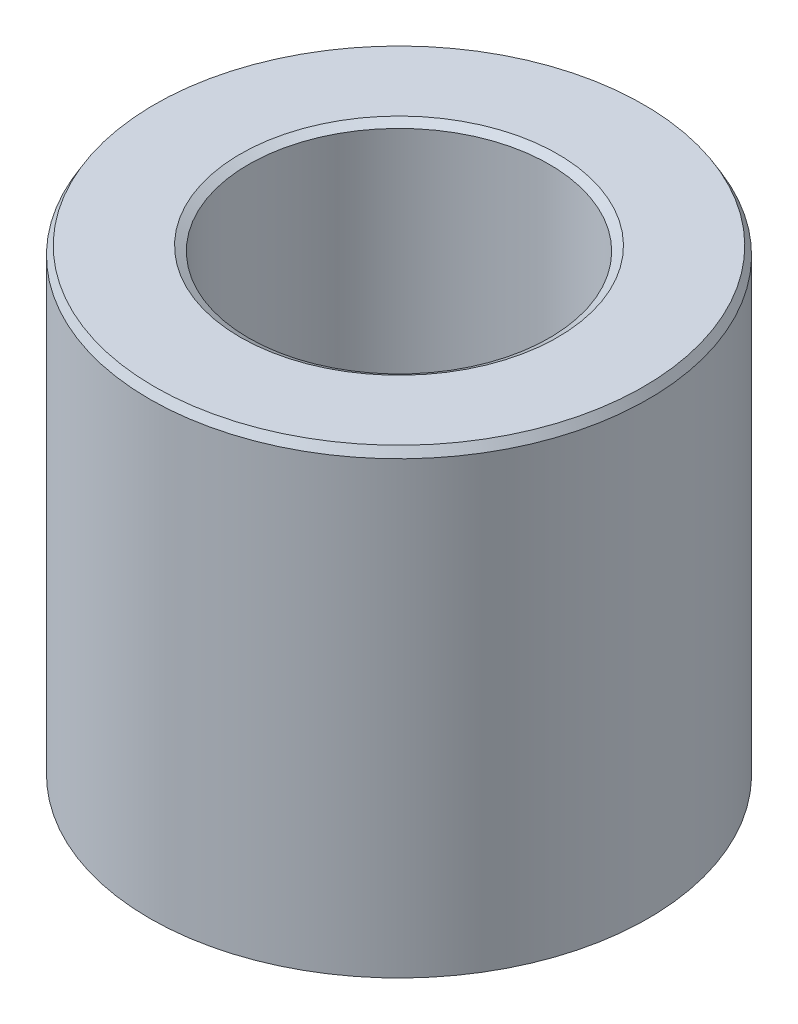
SolidWorks part; units mm, degrees
ref_plane "Front Plane" through (0, 0, 0) normal (0, 0, 1) x (1, 0, 0)
ref_plane "Top Plane" through (0, 0, 0) normal (0, 1, 0) x (1, 0, 0)
ref_plane "Right Plane" through (0, 0, 0) normal (1, 0, 0) x (0, 0, -1)
sketch "Sketch1" plane through (0, 0, 0) normal (0, 1, 0) x (1, 0, 0)
  circle A0 centre (0, 0) radius 60
  dimension "SLEEVE_OD" = 120
extrude "Boss-Extrude1" add sketch "Sketch1" along normal blind 111.3782
sketch "Sketch2" plane through (0, 0, 0) normal (0, 1, 0) x (1, 0, 0)
  circle A0 centre (0, 0) radius 36.1954
  dimension "BORE_D" = 72.3908
extrude "Cut-Extrude1" cut sketch "Sketch2" along normal through all
chamfer "Chamfer1" distance 2.0054 angle 30 4 edges at (0, 111.3782, 36.1954) (0, 0, 36.1954) (0, 0, 60) (0, 111.3782, 60) first distance on face at (0, 111.3782, 36.1954) first distance on face at (0, 0, 36.1954) first distance on face at (0, 111.3782, 60)
